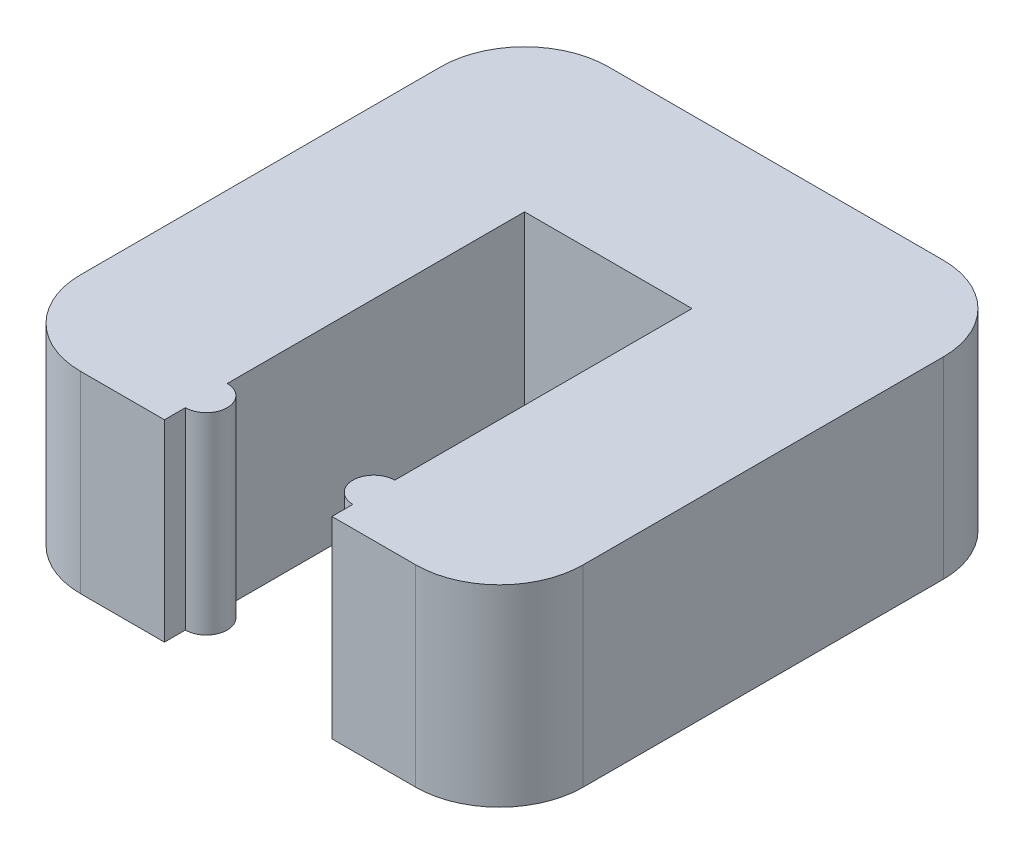
SolidWorks part; units mm, degrees
ref_plane "Front Plane" through (0, 0, 0) normal (0, 0, 1) x (1, 0, 0)
ref_plane "Top Plane" through (0, 0, 0) normal (0, 1, 0) x (1, 0, 0)
ref_plane "Right Plane" through (0, 0, 0) normal (1, 0, 0) x (0, 0, -1)
sketch "Sketch1" plane through (0, 0, 0) normal (0, 1, 0) x (1, 0, 0)
  line L0 (-1, -2.15) -> (-2, -2.15)
  line L2 (-1, -2.15) -> (-1, 2.15)
  line L3 (-1, 2.15) -> (1, 2.15)
  line L4 (1, -2.15) -> (1, 2.15)
  line L5 (-1, -2.15) -> (1, 2.15) construction
  line L6 (-1, 2.15) -> (1, -2.15) construction
  line L7 (-3, -1.15) -> (-3, 3.15)
  line L8 (-2, 4.15) -> (2, 4.15)
  line L9 (3, 3.15) -> (3, -1.15)
  line L10 (2, -2.15) -> (1, -2.15)
  arc A0 (-2, -2.15) -> (-3, -1.15) centre (-2, -1.15) cw
  arc A1 (3, -1.15) -> (2, -2.15) centre (2, -1.15) cw
  arc A2 (2, 4.15) -> (3, 3.15) centre (2, 3.15) cw
  arc A3 (-3, 3.15) -> (-2, 4.15) centre (-2, 3.15) cw
  point P0 (0, 0)
  point P12 (-3, -2.15)
  point P19 (-3, 4.15)
  dimension "D5" = 1
  dimension "D1" = 2
  dimension "D2" = 4.3
  dimension "D3" = 2
  dimension "D4" = 2
base flange "Base-Flange1" sketch "Sketch1" thickness 2.3 reverse thickness direction no parameters "D1"=0.7366
sketch "Sketch6" plane through (0, 0, 0) normal (0, 1, 0) x (1, 0, 0)
  line L0 (-1, -2.15) -> (-1, 2.15) construction
  line L1 (0, 0) -> (0, 0.596) construction
  line L2 (-1, -1.9) -> (-1, -1.4)
  line L3 (1, -1.9) -> (1, -1.4)
  arc A0 (-1, -1.4) -> (-1, -1.9) centre (-1, -1.65) cw
  arc A1 (1, -1.4) -> (1, -1.9) centre (1, -1.65) ccw
  dimension "D1" = 0.25
  dimension "D2" = 0.5
base flange "Tab1" sketch "Sketch6" thickness 2.3 reverse thickness direction no parameters "D1"=0.7366
sketch "Bend-Lines1" [suppressed] plane through (0, 0, 0) normal (0, 1, 0) x (1, 0, 0)
sketch "Bounding-Box1" [suppressed] plane through (0, 0, 0) normal (0, 1, 0) x (1, 0, 0)
sheet metal parameters "Sheet-Metal1" thickness 2.3 parameters "D1"=0.7366
flat pattern "Flat-Pattern1" [suppressed]
sketch "Bend-Lines2" plane through (0, 0, 0) normal (0, 1, 0) x (1, 0, 0)
sketch3d "Bounding-Box2" [suppressed]
  line L0 (1, -1, 0) -> (1, 5.3, 0) construction
  line L1 (-5, -1, 0) -> (-5, 5.3, 0) construction
  line L2 (1, -1, 0) -> (-5, -1, 0) construction
  line L3 (1, 5.3, 0) -> (-5, 5.3, 0) construction
sheet metal parameters "Sheet-Metal2" thickness 2.3 parameters "D1"=0.7366
flat pattern "Flat-Pattern2"
sketch "Bend-Lines3" plane through (0, 0, 0) normal (0, 1, 0) x (1, 0, 0)
sketch3d "Bounding-Box3" [suppressed]
  line L0 (-1, -1, 0) -> (-1, 5.3, 0) construction
  line L1 (5, -1, 0) -> (5, 5.3, 0) construction
  line L2 (-1, -1, 0) -> (5, -1, 0) construction
  line L3 (-1, 5.3, 0) -> (5, 5.3, 0) construction
